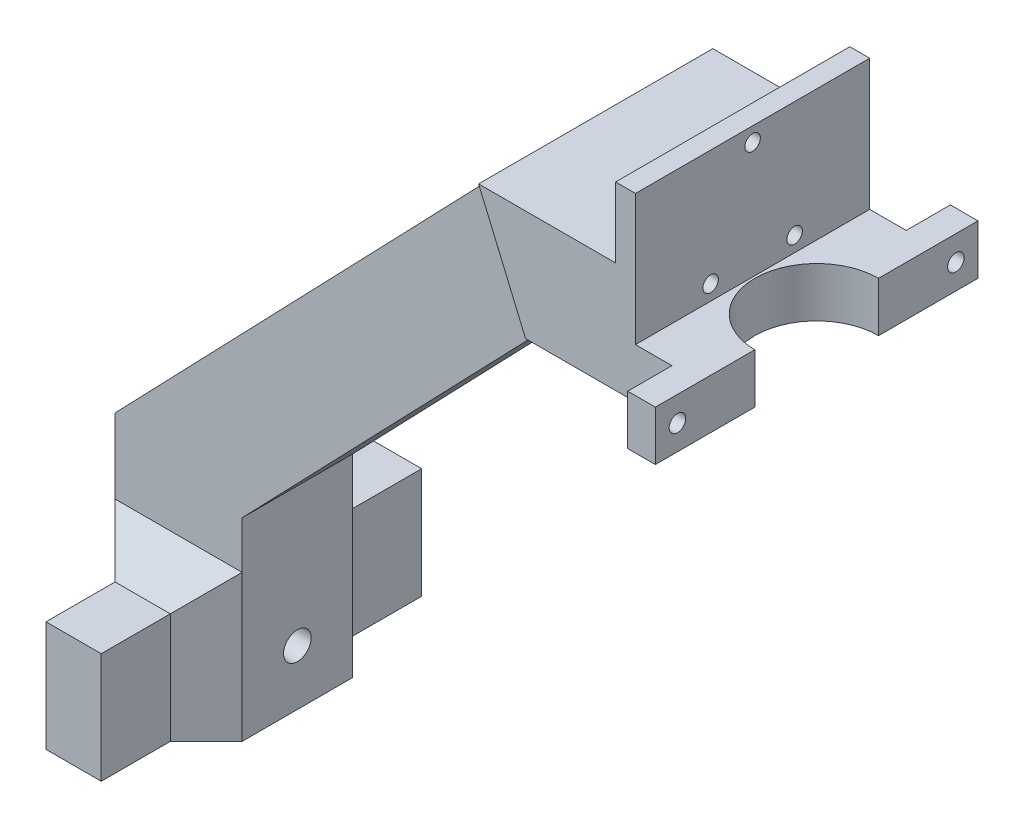
SolidWorks part; units mm, degrees
ref_plane "Front Plane" through (0, 0, 0) normal (0, 0, 1) x (1, 0, 0)
ref_plane "Top Plane" through (0, 0, 0) normal (0, 1, 0) x (1, 0, 0)
ref_plane "Right Plane" through (0, 0, 0) normal (1, 0, 0) x (0, 0, -1)
sketch "Sketch2" plane through (0, 0, 0) normal (0, 0, 1) x (1, 0, 0)
  line L1 (0, 0) -> (50.8, 0)
  line L2 (50.8, 0) -> (50.8, -25.4)
  line L3 (50.8, -25.4) -> (10.8064, -25.4)
  line L6 (-97.79, -101.6) -> (-97.79, -152.4)
  line L7 (-97.79, -152.4) -> (-68.58, -152.4)
  line L13 (-68.58, -152.4) -> (-68.58, -107.8794)
  line L19 (-97.79, -101.6) -> (0, 0)
  line L20 (10.8064, -25.4) -> (-68.58, -107.8794)
  point P0 (0, 0)
  point P1 (50.8, 0)
  point P3 (-97.79, -101.6)
  dimension "D1" = 50.8
  dimension "D2" = 97.79
  dimension "D3" = 101.6
  dimension "D4" = 25.4
  dimension "D5" = 25.4
  dimension "D6" = 50.8
  dimension "D7" = 29.21
extrude "Boss-Extrude1" add sketch "Sketch2" along normal blind 25.4
sketch "Sketch7" plane through (0, 0, 25.4) normal (0, 0, 1) x (1, 0, 0)
  line L0 (-97.79, -152.4) -> (-68.58, -152.4) construction
  line L1 (-89.535, -152.4) -> (-76.835, -152.4)
  line L2 (-89.535, -152.4) -> (-89.535, -127)
  line L3 (-89.535, -127) -> (-76.835, -127)
  line L4 (-76.835, -152.4) -> (-76.835, -127)
  point P6 (-83.185, -152.4)
  dimension "D1" = 12.7
  dimension "D3" = 25.4
extrude "Boss-Extrude4" add sketch "Sketch7" along normal blind 24.13 and the other way blind 49.53
sketch "Sketch8" plane through (-97.79, 0, 0) normal (-1, 0, 0) x (0, 0, 1)
  line L0 (25.4, -152.4) -> (0, -152.4) construction
  line L1 (0, -152.4) -> (0, -127) construction
  circle A0 centre (12.7, -139.7) radius 3.175
  dimension "D1" = 6.35
  dimension "D2" = 12.7
  dimension "D3" = 12.7
extrude "Cut-Extrude3" cut sketch "Sketch8" against normal through all
chamfer "Chamfer3" distance 8.255 angle 45 6 edges at (-76.835, -139.7, 25.4) (-76.835, -139.7, 0) (-83.185, -127, 25.4) (-83.185, -127, 0) (-89.535, -139.7, 25.4) (-89.535, -139.7, 0)
sketch "Sketch9" plane through (0, 0, 0) normal (0, 1, 0) x (1, 0, 0)
  line L0 (50.8, -25.4) -> (50.8, 0) construction
  circle A0 centre (50.8, -12.7) radius 14.224
  circle A1 centre (50.8, -12.7) radius 20.574
  dimension "D1" = 28.448
  dimension "D2" = 41.148
sketch "Sketch10" plane through (0, 0, 25.4) normal (0, 0, 1) x (1, 0, 0)
  line L0 (0, 0) -> (10.8064, -25.4)
  line L1 (50.8, -25.4) -> (10.8064, -25.4)
  line L2 (50.8, -25.4) -> (50.8, 0)
  line L3 (50.8, 0) -> (0, 0)
extrude "Boss-Extrude5" add sketch "Sketch10" along normal blind 14.224 and the other way blind 39.624
extrude "Cut-Extrude4" cut sketch "Sketch9" against normal through all contours A0
sketch "Sketch11" plane through (0, 0, 0) normal (0, 1, 0) x (1, 0, 0)
  line L0 (50.8, 14.224) -> (0, 14.224) construction
  line L1 (50.8, -39.624) -> (36.068, -39.624)
  line L2 (50.8, -39.624) -> (50.8, 14.224)
  line L3 (50.8, 14.224) -> (36.068, 14.224)
  line L4 (36.068, -39.624) -> (36.068, 14.224)
  dimension "D1" = 14.732
extrude "Cut-Extrude5" cut sketch "Sketch11" against normal blind 13.97
chamfer "Chamfer5" distance 13.97 angle 45 2 edges at (5.4032, -12.7, 0) (5.4032, -12.7, 25.4)
sketch "Sketch18" plane through (0, 0, 39.624) normal (0, 0, 1) x (1, 0, 0)
  line L0 (10.8064, -25.4) -> (50.8, -25.4) construction
  line L1 (50.8, -13.97) -> (44.45, -13.97)
  line L2 (50.8, -13.97) -> (50.8, -25.4)
  line L3 (50.8, -25.4) -> (44.45, -25.4)
  line L4 (44.45, -13.97) -> (44.45, -25.4)
  dimension "D1" = 6.35
extrude "Boss-Extrude6" add sketch "Sketch18" along normal blind 10.16
sketch "Sketch19" plane through (0, 0, -14.224) normal (0, 0, -1) x (-1, 0, 0)
  line L0 (-10.8064, -25.4) -> (-50.8, -25.4) construction
  line L1 (-50.8, -13.97) -> (-44.45, -13.97)
  line L2 (-50.8, -13.97) -> (-50.8, -25.4)
  line L3 (-50.8, -25.4) -> (-44.45, -25.4)
  line L4 (-44.45, -13.97) -> (-44.45, -25.4)
  dimension "D1" = 6.35
extrude "Boss-Extrude7" add sketch "Sketch19" along normal blind 10.16
sketch "Sketch20" plane through (50.8, 0, 0) normal (1, 0, 0) x (0, 0, -1)
  line L0 (-49.784, -25.4) -> (-49.784, -13.97) construction
  line L1 (-49.784, -13.97) -> (-26.924, -13.97) construction
  line L2 (24.384, -13.97) -> (24.384, -25.4) construction
  circle A0 centre (-44.704, -19.685) radius 1.905
  circle A1 centre (19.304, -19.685) radius 1.905
  dimension "D1" = 3.81
  dimension "D2" = 5.08
  dimension "D3" = 5.715
  dimension "D4" = 5.08
extrude "Cut-Extrude7" cut sketch "Sketch20" against normal blind 10.16
sketch "Sketch21" plane through (0, 0, 0) normal (0, 1, 0) x (1, 0, 0)
  line L0 (36.068, 14.224) -> (0, 14.224) construction
  line L1 (36.068, -39.624) -> (31.496, -39.624)
  line L2 (36.068, -39.624) -> (36.068, 14.224)
  line L3 (36.068, 14.224) -> (31.496, 14.224)
  line L4 (31.496, -39.624) -> (31.496, 14.224)
  dimension "D1" = 4.572
extrude "Boss-Extrude8" add sketch "Sketch21" along normal blind 16.129
sketch "Sketch22" plane through (36.068, 0, 0) normal (1, 0, 0) x (0, 0, -1)
  line L0 (14.224, -13.97) -> (14.224, 16.129) construction
  line L1 (-39.624, 16.129) -> (14.224, 16.129) construction
  line L2 (14.224, -13.97) -> (-39.624, -13.97) construction
  circle A0 centre (-12.7, 12.827) radius 1.778
  circle A1 centre (-22.352, -10.4775) radius 1.778
  circle A2 centre (-3.048, -10.4775) radius 1.778
  dimension "D1" = 3.556
  dimension "D3" = 3.302
  dimension "D2" = 26.924
  dimension "D4" = 3.4925
  dimension "D5" = 3.4925
  dimension "D6" = 19.304
  dimension "D7" = 9.652
extrude "Cut-Extrude8" cut sketch "Sketch22" against normal blind 4.318
sketch "Sketch23" plane through (31.75, 0, 0) normal (1, 0, 0) x (0, 0, -1)
  circle A0 centre (-22.352, -10.4775) radius 2.794
  circle A1 centre (-3.048, -10.4775) radius 2.794
  dimension "D1" = 5.588
extrude "Cut-Extrude9" cut sketch "Sketch23" against normal through all
